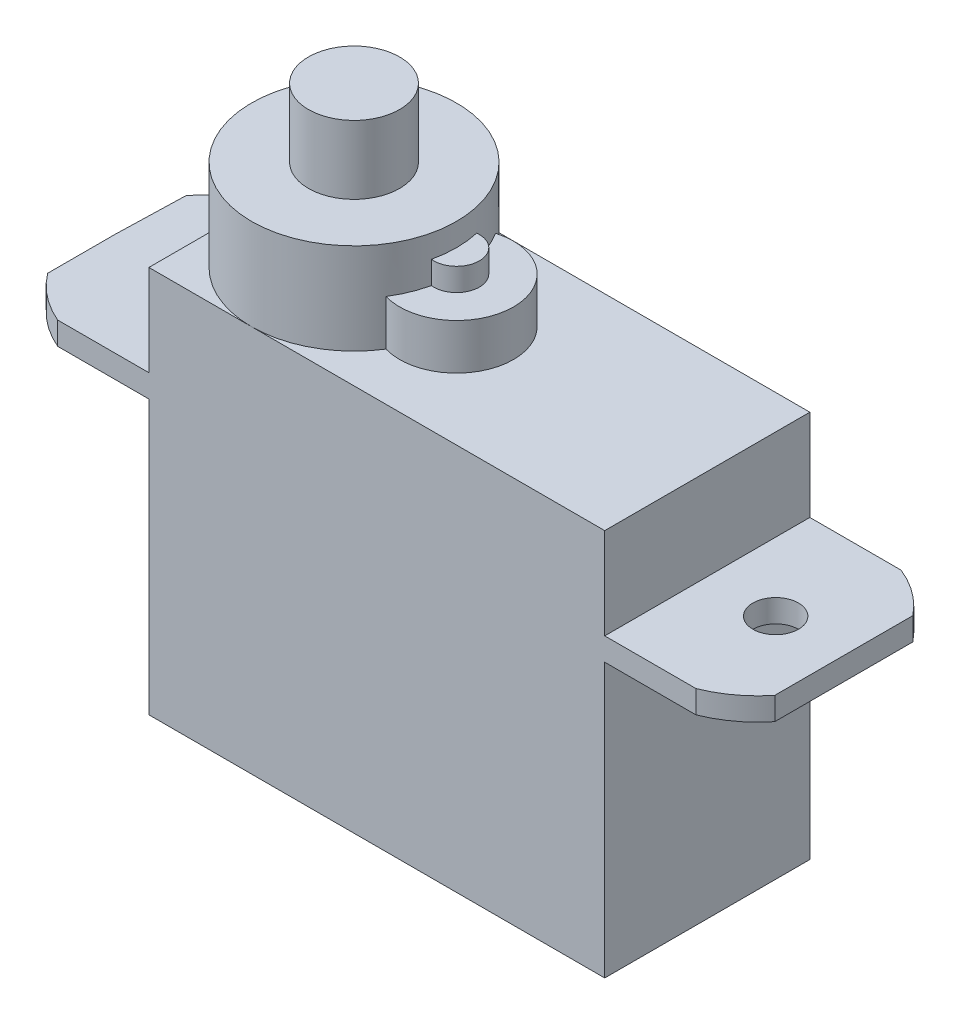
SolidWorks part; units mm, degrees
ref_plane "Front Plane" through (0, 0, 0) normal (0, 0, 1) x (1, 0, 0)
ref_plane "Top Plane" through (0, 0, 0) normal (0, 1, 0) x (1, 0, 0)
ref_plane "Right Plane" through (0, 0, 0) normal (1, 0, 0) x (0, 0, -1)
sketch "Sketch1" plane through (0, 0, 0) normal (0, 1, 0) x (1, 0, 0)
  line L0 (14, 0) -> (17, 0) construction
  line L1 (-10, -4.5) -> (10, -4.5)
  line L2 (-10, -4.5) -> (-10, 4.5)
  line L3 (-10, 4.5) -> (10, 4.5)
  line L4 (10, -4.5) -> (10, 4.5)
  line L5 (-10, -4.5) -> (10, 4.5) construction
  line L6 (-10, 4.5) -> (10, -4.5) construction
  line L7 (-10, -4.5) -> (-14, -4.5)
  line L8 (-10, -4.5) -> (-10, 4.5)
  line L9 (-10, 4.5) -> (-14, 4.5)
  line L10 (-14, -4.5) -> (-14, 4.5)
  line L11 (10, -4.5) -> (14, -4.5)
  line L12 (10, -4.5) -> (10, 4.5)
  line L13 (10, 4.5) -> (14, 4.5)
  line L14 (14, -4.5) -> (14, 4.5)
  line L15 (-14, 0) -> (-17, 0) construction
  line L16 (-10, 0) -> (-13, 0) construction
  line L17 (-10, 0) -> (-5.5, 0) construction
  line L18 (-5.5, 0) -> (-1, 0) construction
  line L20 (10, 0) -> (13, 0) construction
  arc A0 (-14, 4.5) -> (-14, -4.5) centre (-12.1019, 0) ccw
  arc A1 (14, 4.5) -> (14, -4.5) centre (12.212, 0) cw
  circle A2 centre (-5.5, 0) radius 4.5
  circle A3 centre (-1, 0) radius 2.5
  circle A4 centre (-1, 0) radius 1
  circle A5 centre (13, 0) radius 1
  circle A6 centre (-13, 0) radius 1
  circle A7 centre (-5.5, 0) radius 2
  point P0 (0, 0)
  dimension "D1" = 20
  dimension "D2" = 9
  dimension "D3" = 4
  dimension "D4" = 4
extrude "Boss-Extrude3" add sketch "Sketch1" along normal blind 4 and the other way blind 13 contours A3 A2 L1 L4 L3 | A2 L2 L1 | A2 L3 L8 | A3 A7 A2 | A7 | A4 A2 A3 | A4 A2 A3 | A2 A4 | A2 A4 region at (-8.9948, 0, 3.4948) region at (4.4349, 0, 0) region at (-5.5, 0, 0) region at (-8.5954, 0, 3.0954) region at (-8.9948, 0, -3.4948) region at (-2.329, 0, 0) region at (0.0181, 0, 0) region at (-1.4438, 0, 0) region at (-0.5962, 0, 0)
extrude "Boss-Extrude4" add sketch "Sketch1<3>" along normal blind 0.0001 and the other way blind 1 contours L10 A6 L7 L2 L8 L9 | L14 A5 L13 L4 L11 | A1 L14 | L10 A0 region at (-11.9044, 0, 0) region at (-15.2325, 0, 0) region at (11.9044, 0, 0) region at (15.2622, 0, 0)
sketch "Sketch1<3>" plane through (0, 0, 0) normal (0, 1, 0) x (1, 0, 0) same geometry as "Sketch1"
extrude "Boss-Extrude6" add sketch "Sketch1<8>" along normal blind 7 contours A2 A4 | A2 A4 region at (-1.4438, 0, 0) region at (-0.5962, 0, 0)
sketch "Sketch1<8>" plane through (0, 0, 0) normal (0, 1, 0) x (1, 0, 0) same geometry as "Sketch1"
extrude "Boss-Extrude7" add sketch "Sketch1<9>" along normal blind 11 contours A7 region at (-5.5, 0, 0)
sketch "Sketch1<9>" plane through (0, 0, 0) normal (0, 1, 0) x (1, 0, 0) same geometry as "Sketch1"
extrude "Boss-Extrude10" add sketch "Sketch1<11>" along normal blind 8 contours A3 A7 A2 | A7 | A4 A2 A3 | A2 A4 region at (-5.5, 0, 0) region at (-8.5954, 0, 3.0954) region at (-2.329, 0, 0) region at (-1.4438, 0, 0)
sketch "Sketch1<11>" plane through (0, 0, 0) normal (0, 1, 0) x (1, 0, 0) same geometry as "Sketch1"
extrude "Boss-Extrude11" add sketch "Sketch1<12>" along normal blind 6 contours A4 A2 A3 | A2 A4 | A4 A2 A3 | A2 A4 region at (-2.329, 0, 0) region at (0.0181, 0, 0) region at (-1.4438, 0, 0) region at (-0.5962, 0, 0)
sketch "Sketch1<12>" plane through (0, 0, 0) normal (0, 1, 0) x (1, 0, 0) same geometry as "Sketch1"
sketch "Sketch5" plane through (0, 0.0001, 0) normal (0, 1, 0) x (1, 0, 0)
  line L0 (15.9898, 0) -> (15.9898, 5)
  line L1 (15.9898, 5) -> (17.9898, 5)
  line L2 (17.9898, 5) -> (17.9898, -5)
  line L3 (17.9898, -5) -> (15.9898, -5)
  line L4 (15.9898, -5) -> (15.9898, 0)
  line L5 (-10, 0) -> (-16, 0) construction
  line L6 (-16, 0) -> (-15.8596, 4.998)
  line L7 (-15.8596, 4.998) -> (-17.8588, 5.0542)
  line L8 (-17.8588, 5.0542) -> (-18.1413, -5)
  line L9 (-18.1413, -5) -> (-16, -5)
  line L10 (-16, -5) -> (-16, 0)
extrude "Cut-Extrude1" cut sketch "Sketch5" against normal blind 10 contours L4 L0 L1 L2 L3 | L10 L6 L7 L8 L9
